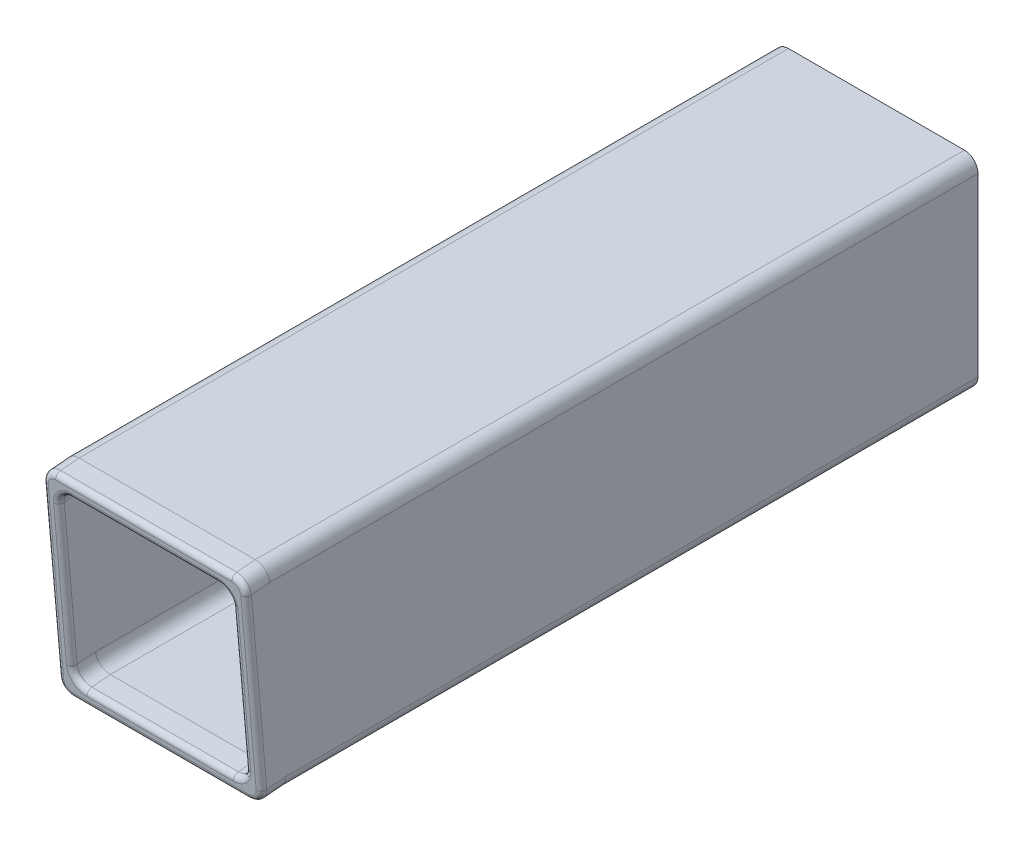
SolidWorks part; units mm, degrees
material "ASTM A500 Grade B Steel"
ref_plane "Front Plane" through (0, 0, 0) normal (0, 0, 1) x (1, 0, 0)
ref_plane "Top Plane" through (0, 0, 0) normal (0, 1, 0) x (1, 0, 0)
ref_plane "Right Plane" through (0, 0, 0) normal (1, 0, 0) x (0, 0, -1)
sketch "Sketch1" plane through (0, 0, 0) normal (0, 0, 1) x (1, 0, 0)
  line L0 (5.3086, -2.7686) -> (32.7914, -2.7686)
  line L1 (2.54, 0) -> (35.56, 0)
  line L2 (0, -2.54) -> (0, -35.56)
  line L3 (2.54, -38.1) -> (35.56, -38.1)
  line L4 (38.1, -2.54) -> (38.1, -35.56)
  line L5 (35.3314, -5.3086) -> (35.3314, -32.7914)
  line L6 (5.3086, -35.3314) -> (32.7914, -35.3314)
  line L7 (2.7686, -5.3086) -> (2.7686, -32.7914)
  line L8 (0, 0) -> (0, -38.1) construction
  line L9 (0, -38.1) -> (38.1, -38.1) construction
  line L10 (38.1, 0) -> (38.1, -38.1) construction
  line L11 (2.7686, -2.7686) -> (2.7686, -35.3314) construction
  line L12 (2.7686, -35.3314) -> (35.3314, -35.3314) construction
  line L13 (35.3314, -2.7686) -> (35.3314, -35.3314) construction
  line L14 (2.7686, -2.7686) -> (35.3314, -2.7686) construction
  line L15 (0, 0) -> (38.1, 0) construction
  arc A0 (0, -35.56) -> (2.54, -38.1) centre (2.54, -35.56) ccw
  arc A1 (38.1, -35.56) -> (35.56, -38.1) centre (35.56, -35.56) cw
  arc A2 (2.7686, -32.7914) -> (5.3086, -35.3314) centre (5.3086, -32.7914) ccw
  arc A3 (32.7914, -35.3314) -> (35.3314, -32.7914) centre (32.7914, -32.7914) ccw
  arc A4 (35.3314, -5.3086) -> (32.7914, -2.7686) centre (32.7914, -5.3086) ccw
  arc A5 (38.1, -2.54) -> (35.56, 0) centre (35.56, -2.54) ccw
  arc A6 (0, -2.54) -> (2.54, 0) centre (2.54, -2.54) cw
  arc A7 (5.3086, -2.7686) -> (2.7686, -5.3086) centre (5.3086, -5.3086) ccw
  point P12 (0, -38.1)
  dimension "D4" = 2.54
  dimension "D3" = 2.7686
extrude "Boss-Extrude1" add sketch "Sketch1" along normal blind 133
sketch "Sketch2" plane through (38.1, 0, 0) normal (1, 0, 0) x (0, 0, -1)
  line L0 (-133, 0) -> (-129.6667, -38.1)
  line L1 (-133, -38.1) -> (0, -38.1) construction
  line L2 (-129.6667, -38.1) -> (-133, -38.1)
  line L3 (-133, -38.1) -> (-133, 0)
  dimension "D1" = 5
extrude "Cut-Extrude1" cut sketch "Sketch2" against normal through all
sketch "Sketch3" plane through (0, -11.5476, 131.9897) normal (0, -0.0872, 0.9962) x (1, 0, 0)
  line L0 (35.3314, 6.2628) -> (35.3314, -21.3249) construction
  line L1 (32.7914, -23.8746) -> (5.3086, -23.8746) construction
  line L2 (2.7686, -21.3249) -> (2.7686, 6.2628) construction
  line L3 (5.3086, 8.8125) -> (32.7914, 8.8125) construction
  line L4 (2.54, -26.6538) -> (35.56, -26.6538)
  line L5 (38.1, -24.1041) -> (38.1, 9.042)
  line L6 (35.56, 11.5917) -> (2.54, 11.5917)
  line L7 (0, 9.042) -> (0, -24.1041)
  line L8 (2.54, -26.6538) -> (35.56, -26.6538)
  line L9 (38.1, -24.1041) -> (38.1, 9.042)
  line L10 (35.56, 11.5917) -> (2.54, 11.5917)
  line L11 (0, 9.042) -> (0, -24.1041)
  line L12 (35.3314, 6.2628) -> (35.3314, -21.3249)
  line L13 (32.7914, -23.8746) -> (5.3086, -23.8746)
  line L14 (2.7686, -21.3249) -> (2.7686, 6.2628)
  line L15 (5.3086, 8.8125) -> (32.7914, 8.8125)
  ellipse E0 centre (32.7914, 6.2628) end of major axis (32.7914, 8.8125) minor radius 2.54 (35.3314, 6.2628) -> (32.7914, 8.8125) ccw construction
  ellipse E1 centre (32.7914, -21.3249) end of major axis (32.7914, -23.8746) minor radius 2.54 (32.7914, -23.8746) -> (35.3314, -21.3249) ccw construction
  ellipse E2 centre (5.3086, -21.3249) end of major axis (5.3086, -23.8746) minor radius 2.54 (2.7686, -21.3249) -> (5.3086, -23.8746) ccw construction
  ellipse E3 centre (5.3086, 6.2628) end of major axis (5.3086, 3.7131) minor radius 2.54 (5.3086, 8.8125) -> (2.7686, 6.2628) ccw construction
  ellipse E4 centre (35.56, -24.1041) end of major axis (35.56, -26.6538) minor radius 2.54 (35.56, -26.6538) -> (38.1, -24.1041) ccw
  ellipse E5 centre (35.56, 9.042) end of major axis (35.56, 6.4923) minor radius 2.54 (38.1, 9.042) -> (35.56, 11.5917) ccw
  ellipse E6 centre (2.54, 9.042) end of major axis (2.54, 11.5917) minor radius 2.54 (2.54, 11.5917) -> (0, 9.042) ccw
  ellipse E7 centre (2.54, -24.1041) end of major axis (2.54, -26.6538) minor radius 2.54 (0, -24.1041) -> (2.54, -26.6538) ccw
  ellipse E8 centre (35.56, -24.1041) end of major axis (35.56, -26.6538) minor radius 2.54 (35.56, -26.6538) -> (38.1, -24.1041) ccw
  ellipse E9 centre (35.56, 9.042) end of major axis (35.56, 6.4923) minor radius 2.54 (38.1, 9.042) -> (35.56, 11.5917) ccw
  ellipse E10 centre (2.54, 9.042) end of major axis (2.54, 11.5917) minor radius 2.54 (2.54, 11.5917) -> (0, 9.042) ccw
  ellipse E11 centre (2.54, -24.1041) end of major axis (2.54, -26.6538) minor radius 2.54 (0, -24.1041) -> (2.54, -26.6538) ccw
  ellipse E12 centre (32.7914, 6.2628) end of major axis (32.7914, 8.8125) minor radius 2.54 (35.3314, 6.2628) -> (32.7914, 8.8125) ccw
  ellipse E13 centre (32.7914, -21.3249) end of major axis (32.7914, -23.8746) minor radius 2.54 (32.7914, -23.8746) -> (35.3314, -21.3249) ccw
  ellipse E14 centre (5.3086, -21.3249) end of major axis (5.3086, -23.8746) minor radius 2.54 (2.7686, -21.3249) -> (5.3086, -23.8746) ccw
  ellipse E15 centre (5.3086, 6.2628) end of major axis (5.3086, 3.7131) minor radius 2.54 (5.3086, 8.8125) -> (2.7686, 6.2628) ccw
  dimension "D1" = 0
extrude "Boss-Extrude2" add sketch "Sketch3" along normal up to surface (4.4808 mm away)
fillet "Fillet1" radius 1 16 edges at (0.7439, -1.1345, 137.3987) (19.05, -0.3905, 137.4638) (37.3561, -1.1345, 137.3987) (38.1, -19.4405, 135.7971) (37.3561, -37.7466, 134.1956) (19.05, -38.4905, 134.1305) (0.7439, -37.7466, 134.1956) (0, -19.4405, 135.7971) (19.05, -3.1591, 137.2216) (3.5125, -3.9031, 137.1565) (2.7686, -19.4405, 135.7971) (3.5125, -34.978, 134.4378) (19.05, -35.7219, 134.3727) (34.5875, -34.978, 134.4378) (35.3314, -19.4405, 135.7971) (34.5875, -3.9031, 137.1565)
